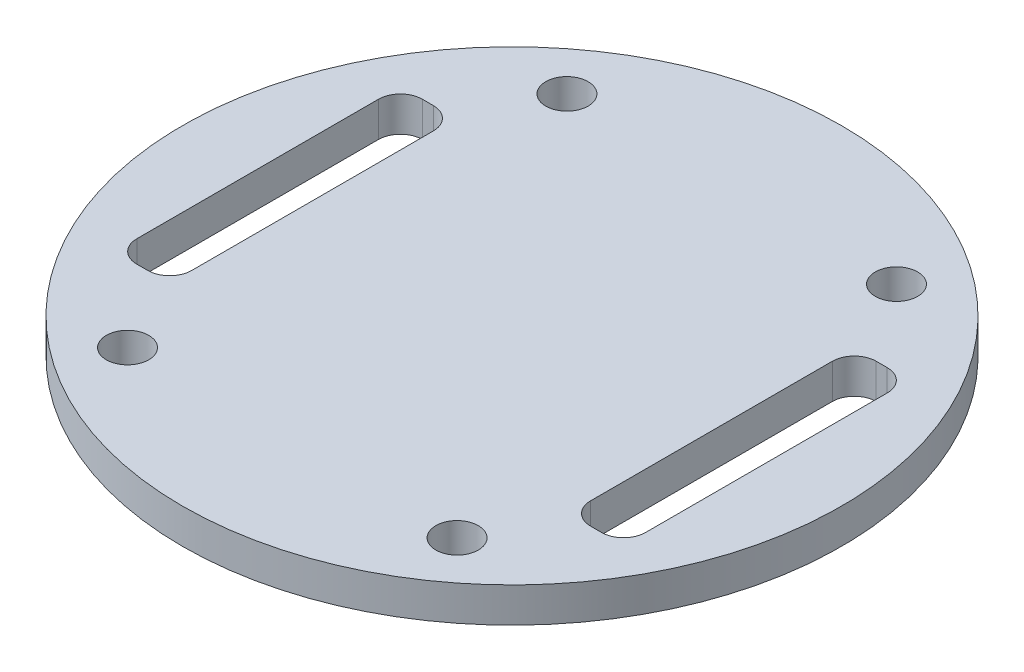
SolidWorks part; units mm, degrees
material "Acrylic (Medium-high impact)"
ref_plane "Front Plane" through (0, 0, 0) normal (0, 0, 1) x (1, 0, 0)
ref_plane "Top Plane" through (0, 0, 0) normal (0, 1, 0) x (1, 0, 0)
ref_plane "Right Plane" through (0, 0, 0) normal (1, 0, 0) x (0, 0, -1)
ref_axis "x-axis" through (88.99, 0, 0) along (-1, 0, 0)
ref_axis "y-axis" through (0, 0, 55) along (0, 0, -1)
ref_axis "z-axis" through (0, 55, 0) along (0, -1, 0)
sketch "Sketch2" plane through (0, 0, 0) normal (0, 1, 0) x (1, 0, 0)
  circle A0 centre (0, 0) radius 30
  dimension "D1" = 60
extrude "AcrylicBase" add sketch "Sketch2" along normal mid plane 3.175
sketch "Sketch3" plane through (0, 1.5875, 0) normal (0, 1, 0) x (1, 0, 0)
  line L0 (0, 30) -> (0, -30) construction
  line L1 (-23.1571, 13) -> (-18.1571, 13)
  line L2 (-23.1571, 13) -> (-23.1571, -13)
  line L3 (-23.1571, -13) -> (-18.1571, -13)
  line L4 (-18.1571, 13) -> (-18.1571, -13)
  line L5 (-23.1571, 13) -> (-18.1571, -13) construction
  line L6 (-18.1571, 13) -> (-23.1571, -13) construction
  line L7 (0, 0) -> (-20.6571, 0) construction
  line L8 (23.1571, -13) -> (18.1571, -13)
  line L9 (23.1571, 13) -> (23.1571, -13)
  line L10 (23.1571, 13) -> (18.1571, 13)
  line L11 (18.1571, 13) -> (18.1571, -13)
  circle A0 centre (0, 0) radius 30 construction
  dimension "D1" = 5
  dimension "D2" = 26
  dimension "D3" = 20.6571
extrude "wheels" cut sketch "Sketch3" against normal through all
fillet "reliefs" radius 2 8 edges at (18.1571, 0, -13) (23.1571, 0, -13) (23.1571, 0, 13) (18.1571, 0, 13) (-23.1571, 0, 13) (-18.1571, 0, 13) (-18.1571, 0, -13) (-23.1571, 0, -13)
sketch "Sketch4" plane through (0, 1.5875, 0) normal (0, 1, 0) x (1, 0, 0)
  circle A0 centre (-15, 20) radius 1.9304 construction
  circle A1 centre (-15, -20) radius 1.9304 construction
  circle A2 centre (15, -20) radius 1.9304 construction
  circle A3 centre (15, 20) radius 1.9304 construction
  circle A4 centre (-15, 20) radius 1.9304
  circle A5 centre (-15, -20) radius 1.9304
  circle A6 centre (15, -20) radius 1.9304
  circle A7 centre (15, 20) radius 1.9304
extrude "Cut-Extrude1" cut sketch "Sketch4" against normal through all
